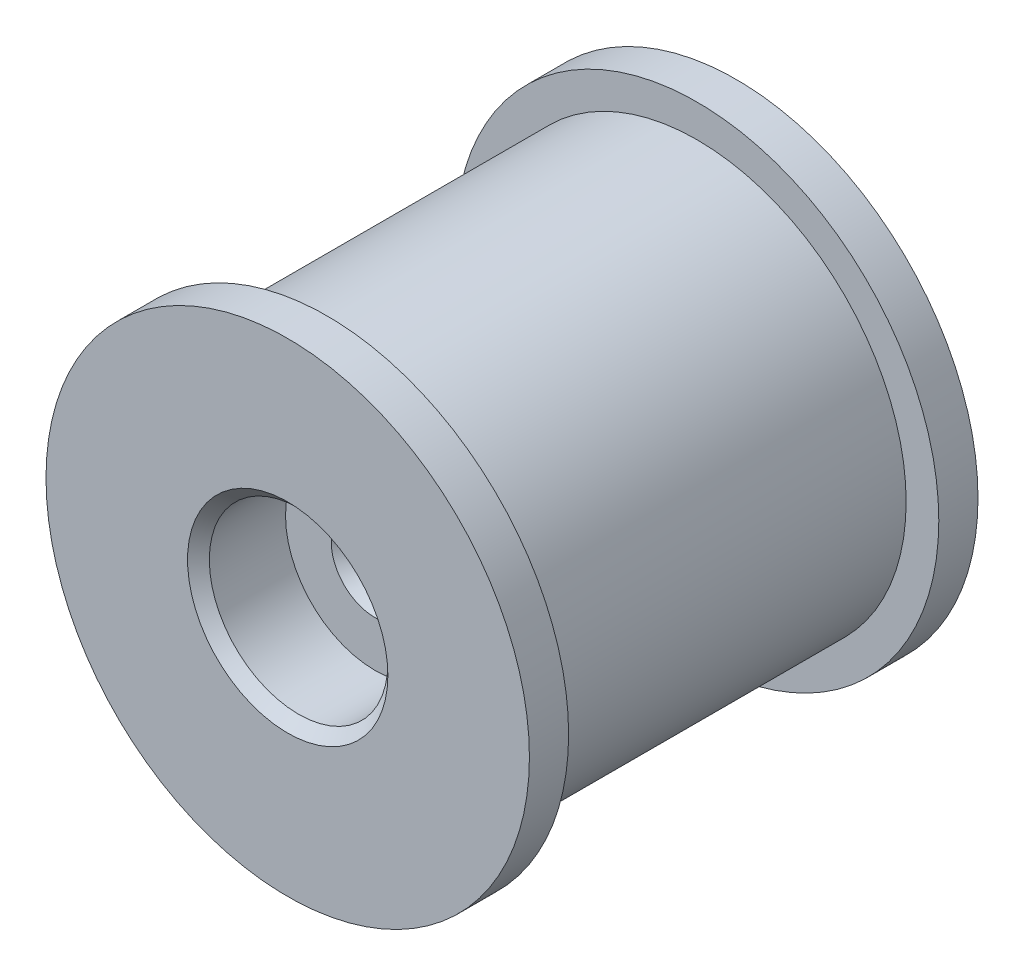
SolidWorks part; units mm, degrees
ref_plane "Ebene vorne" through (0, 0, 0) normal (0, 0, 1) x (1, 0, 0)
ref_plane "Ebene oben" through (0, 0, 0) normal (0, 1, 0) x (1, 0, 0)
ref_plane "Ebene rechts" through (0, 0, 0) normal (1, 0, 0) x (0, 0, -1)
sketch "Skizze1" plane through (0, 0, 0) normal (0, 0, 1) x (1, 0, 0)
  circle A0 centre (0, 0) radius 9.6
  dimension "D1" = 19.2
extrude "Aufsatz-Linear austragen1" add sketch "Skizze1" along normal blind 10.3 and the other way blind 10.3
ref_axis "Rotationsachse" [suppressed] through (0, 0, -9.8) along (0, 0, 1)
sketch "Skizze2" plane through (0, 0, 10.3) normal (0, 0, 1) x (1, 0, 0)
  circle A0 centre (0, 0) radius 11.1
  dimension "D1" = 22.2
extrude "Aufsatz-Linear austragen2" add sketch "Skizze2" against normal blind 1.8
sketch "Skizze3" plane through (0, 0, -10.3) normal (0, 0, -1) x (-1, 0, 0)
  circle A0 centre (0, 0) radius 11.1
  dimension "D1" = 22.2
extrude "Aufsatz-Linear austragen3" add sketch "Skizze3" against normal blind 1.8
sketch "Skizze8" plane through (0, 0, 0) normal (1, 0, 0) x (0, 0, -1)
  line L0 (10.3, 0) -> (10.3, 8)
  line L1 (10.3, -11.1) -> (10.3, 11.1) construction
  line L2 (10.3, 8) -> (8.5, 8)
  line L3 (8.5, 11.1) -> (8.5, -11.1) construction
  line L8 (8.5, 8) -> (-3.7, 4)
  line L9 (-3.7, 4) -> (-3.7, 1.5)
  line L10 (-3.7, 1.5) -> (-6.3, 1.5)
  line L11 (-6.3, 1.5) -> (-6.3, 4.1)
  line L12 (-6.3, 4.1) -> (-10.3, 4.1)
  line L13 (-10.3, 11.1) -> (-10.3, -11.1) construction
  line L14 (-10.3, 4.1) -> (-10.3, 0)
  line L15 (-10.3, 0) -> (10.3, 0)
  dimension "D1" = 8
  dimension "D2" = 4
  dimension "D3" = 4.1
  dimension "D4" = 14
  dimension "D5" = 4
  dimension "D6" = 1.5
revolve "Schnitt-Rotation1" cut sketch "Skizze8" angle 360 about axis through (0, 0, -9.8) along (0, 0, 1)
chamfer "Fase1" distance 0.5 3 edges at (-1.5, 0, 6.3) (-1.5, 0, 3.7) (-4.1, 0, 10.3)
